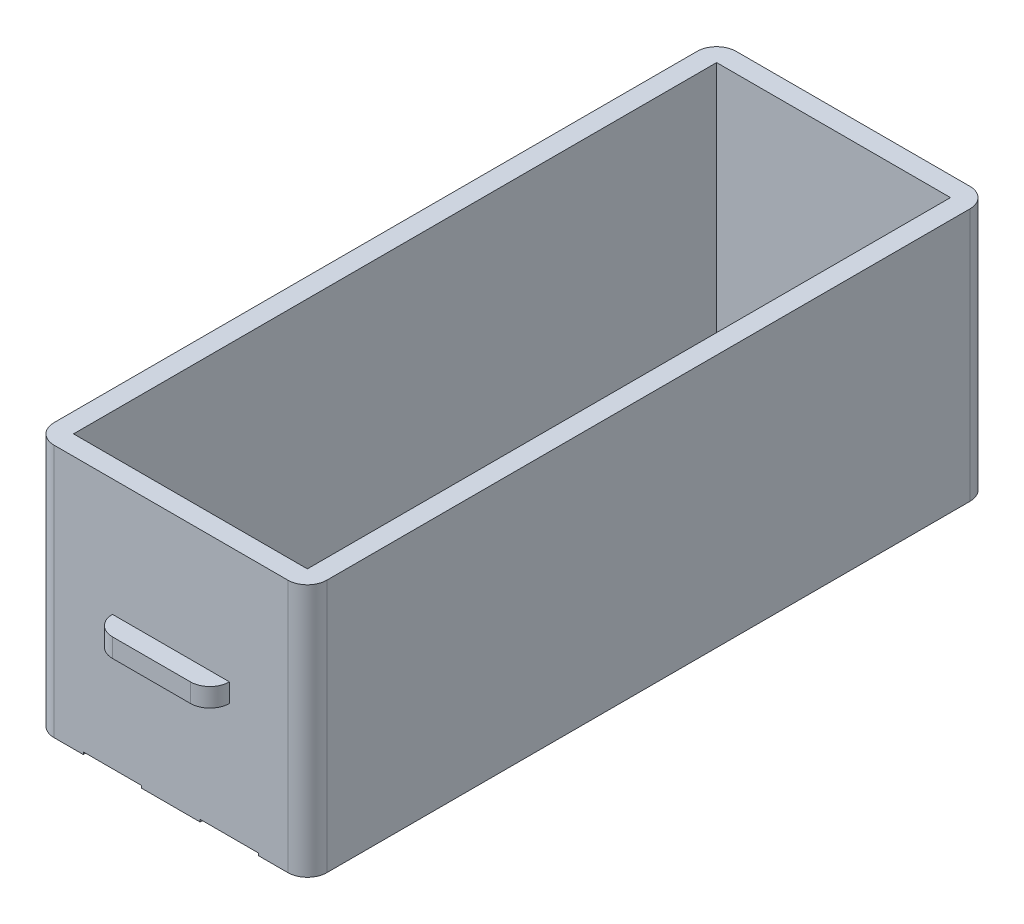
SolidWorks part; units mm, degrees
material "ABS"
ref_plane "Front Plane" through (0, 0, 0) normal (0, 0, 1) x (1, 0, 0)
ref_plane "Top Plane" through (0, 0, 0) normal (0, 1, 0) x (1, 0, 0)
ref_plane "Right Plane" through (0, 0, 0) normal (1, 0, 0) x (0, 0, -1)
sketch "Sketch1" plane through (0, 0, 0) normal (0, 0, 1) x (1, 0, 0)
  line L0 (-44.45, 41.275) -> (-44.45, -41.275)
  line L1 (-44.45, -41.275) -> (44.45, -41.275)
  line L2 (44.45, -41.275) -> (44.45, 41.275)
  line L3 (44.45, 41.275) -> (-44.45, 41.275)
  line L4 (-44.45, 41.275) -> (44.45, -41.275) construction
  line L5 (44.45, 41.275) -> (-44.45, -41.275) construction
  point P2 (0, 0)
  dimension "D1" = 88.9
  dimension "D2" = 82.55
extrude "Boss-Extrude1" add sketch "Sketch1" along normal mid plane 222.25
sketch "Sketch2" plane through (0, 41.275, 0) normal (0, 1, 0) x (1, 0, 0)
  line L0 (-38.1, 104.775) -> (-38.1, -104.775)
  line L1 (-38.1, -104.775) -> (38.1, -104.775)
  line L2 (38.1, -104.775) -> (38.1, 104.775)
  line L3 (38.1, 104.775) -> (-38.1, 104.775)
  line L4 (-44.45, -111.125) -> (-44.45, 111.125) construction
  line L5 (44.45, -111.125) -> (-44.45, -111.125) construction
  line L6 (44.45, 111.125) -> (-44.45, 111.125) construction
  line L7 (44.45, -111.125) -> (44.45, 111.125) construction
  dimension "D1" = 6.35
  dimension "D2" = 6.35
  dimension "D3" = 6.35
  dimension "D4" = 6.35
extrude "Cut-Extrude1" cut sketch "Sketch2" against normal blind 76.2
sketch "Sketch3" plane through (0, 0, 111.125) normal (0, 0, 1) x (1, 0, 0)
  line L0 (-44.45, 41.275) -> (44.45, -41.275) construction
  line L1 (44.45, -41.275) -> (44.45, 41.275) construction
  line L2 (44.45, 41.275) -> (-44.45, -41.275) construction
  line L3 (-19.05, 3.048) -> (-19.05, -3.048)
  line L4 (-19.05, -3.048) -> (19.05, -3.048)
  line L5 (19.05, -3.048) -> (19.05, 3.048)
  line L6 (19.05, 3.048) -> (-19.05, 3.048)
  line L7 (-19.05, 3.048) -> (19.05, -3.048) construction
  line L8 (19.05, 3.048) -> (-19.05, -3.048) construction
  point P10 (0, 0)
  dimension "D1" = 6.096
  dimension "D2" = 38.1
extrude "Boss-Extrude2" add sketch "Sketch3" along normal mid plane 12.7
sketch "Sketch4" plane through (0, 0, 111.125) normal (0, 0, 1) x (1, 0, 0)
  line L0 (-19.05, 41.275) -> (-19.05, -41.275) construction
  line L1 (44.45, 41.275) -> (-44.45, 41.275) construction
  line L2 (-44.45, -41.275) -> (44.45, -41.275) construction
  line L3 (19.05, 41.275) -> (19.05, -41.275) construction
  line L4 (-44.45, 41.275) -> (-44.45, -41.275) construction
  line L5 (44.45, -41.275) -> (44.45, 41.275) construction
  line L6 (-28.575, -41.275) -> (-28.575, -40.513)
  line L7 (-28.575, -40.513) -> (-9.525, -40.513)
  line L8 (-9.525, -40.513) -> (-9.525, -41.275)
  line L9 (-9.525, -41.275) -> (-28.575, -41.275)
  line L10 (0, 41.275) -> (0, -41.275) construction
  line L11 (9.525, -40.513) -> (9.525, -41.275)
  line L12 (28.575, -40.513) -> (9.525, -40.513)
  line L13 (28.575, -41.275) -> (28.575, -40.513)
  line L14 (9.525, -41.275) -> (28.575, -41.275)
  point P14 (-19.05, -41.275)
  dimension "D1" = 25.4
  dimension "D2" = 25.4
  dimension "D3" = 0.762
  dimension "D4" = 19.05
extrude "Cut-Extrude2" cut sketch "Sketch4" against normal through all
fillet "Fillet1" radius 6.35 4 edges at (44.45, 0, -111.125) (-44.45, 0, -111.125) (-44.45, 0, 111.125) (44.45, 0, 111.125)
fillet "Fillet2" radius 6.35 2 edges at (19.05, 0, 117.475) (-19.05, 0, 117.475)
